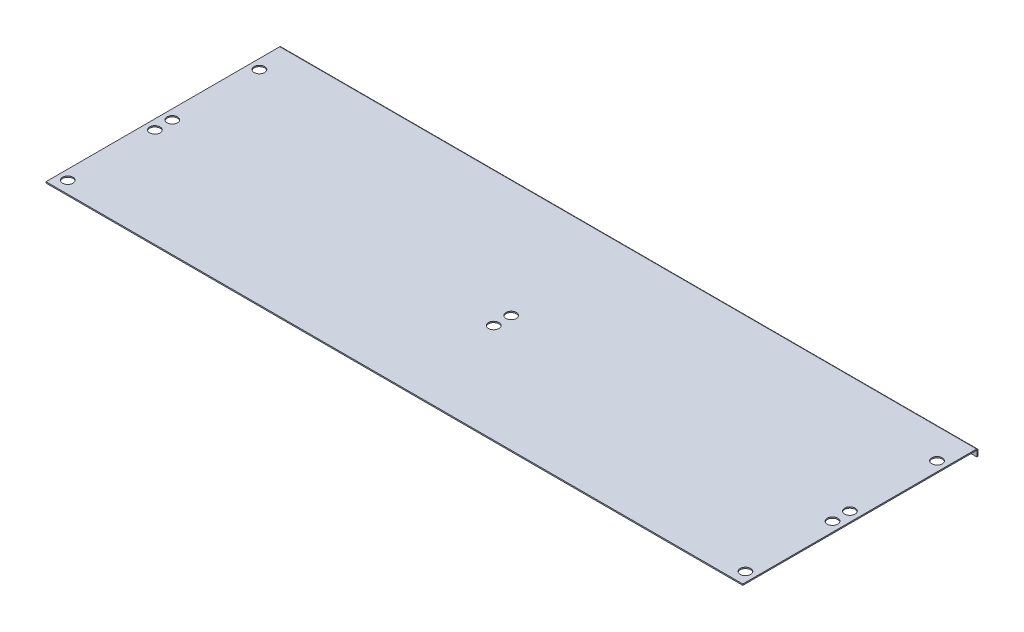
SolidWorks part; units mm, degrees
note: The reader was unsure of these and kept them because the rebuilt part matched: flange length of "边线-法兰1".
ref_plane "前视基准面" through (0, 0, 0) normal (0, 0, 1) x (1, 0, 0)
ref_plane "上视基准面" through (0, 0, 0) normal (0, 1, 0) x (1, 0, 0)
ref_plane "右视基准面" through (0, 0, 0) normal (1, 0, 0) x (0, 0, -1)
sketch "草图1" plane through (0, 0, 0) normal (0, 1, 0) x (1, 0, 0)
  line L0 (0, 67.5) -> (0, -67.5) construction
  line L1 (-200, 67.5) -> (200, 67.5)
  line L2 (-200, 67.5) -> (-200, -67.5)
  line L3 (-200, -67.5) -> (200, -67.5)
  line L4 (200, 67.5) -> (200, -67.5)
  line L5 (-200, 67.5) -> (200, -67.5) construction
  line L6 (-200, -67.5) -> (200, 67.5) construction
  circle A0 centre (-194.5, -60.5) radius 3
  circle A1 centre (-194.5, -10.5) radius 3
  circle A2 centre (-194.5, -0.5) radius 3
  circle A3 centre (-194.5, 49.5) radius 3
  circle A8 centre (0, -10.5) radius 3
  circle A9 centre (0, -0.5) radius 3
  circle A10 centre (194.5, -60.5) radius 3
  circle A11 centre (194.5, -10.5) radius 3
  circle A12 centre (194.5, -0.5) radius 3
  circle A13 centre (194.5, 49.5) radius 3
  point P0 (0, 0)
  dimension "D4" = 7
  dimension "D5" = 6
  dimension "D6" = 5.5
  dimension "D7" = 5.5
  dimension "D8" = 5.5
  dimension "D1" = 400
  dimension "D2" = 135
  dimension "D3" = 5.5
  dimension "D9" = 50
  dimension "D10" = 10
  dimension "D11" = 50
  dimension "D12" = 18
base flange "基体-法兰1" sketch "草图1" thickness 0.7 reverse thickness direction no parameters "D1"=0.2
edge flange "边线-法兰1" sketch "草图10" flange angle 90 flange length 4 flange position material inside bend radius 0.2 thickness 0.7 relief rectangular parameters "D6"=10
sketch "草图10" plane through (0, -0.7, -67.5) normal (0, 0, -1) x (1, 0, 0)
  line L0 (200, 0) -> (-200, 0) construction
  line L1 (200, 0) -> (-200, 0)
  line L2 (-200, 0) -> (-200, 3.3)
  line L3 (-200, 3.3) -> (200, 3.3)
  line L4 (200, 3.3) -> (200, 0)
bend "边线折弯1" bend radius 0.2 bend angle 90 parameters "D5"=1
sketch "折弯-线1" plane through (0, 0, 0) normal (0, 1, 0) x (1, 0, 0)
sketch "边界框1" plane through (0, 0, 0) normal (0, 1, 0) x (1, 0, 0)
sheet metal parameters "钣金6" thickness 0.7 parameters "D1"=0.2
flat pattern "平板型式6" [suppressed]
sketch "折弯-线2" plane through (0, 0, 0) normal (0, 1, 0) x (1, 0, 0)
sketch "边界框2" [suppressed] plane through (0, 0, 0) normal (0, 1, 0) x (1, 0, 0)
sheet metal parameters "钣金7" thickness 0.7 parameters "D1"=0.2
flat pattern "平板型式6" [suppressed]
sketch "折弯-线2" plane through (0, 0, 0) normal (0, 1, 0) x (1, 0, 0)
sketch "边界框2" [suppressed] plane through (0, 0, 0) normal (0, 1, 0) x (1, 0, 0)
bend of the flat pattern "展平-<边线折弯1>1"
